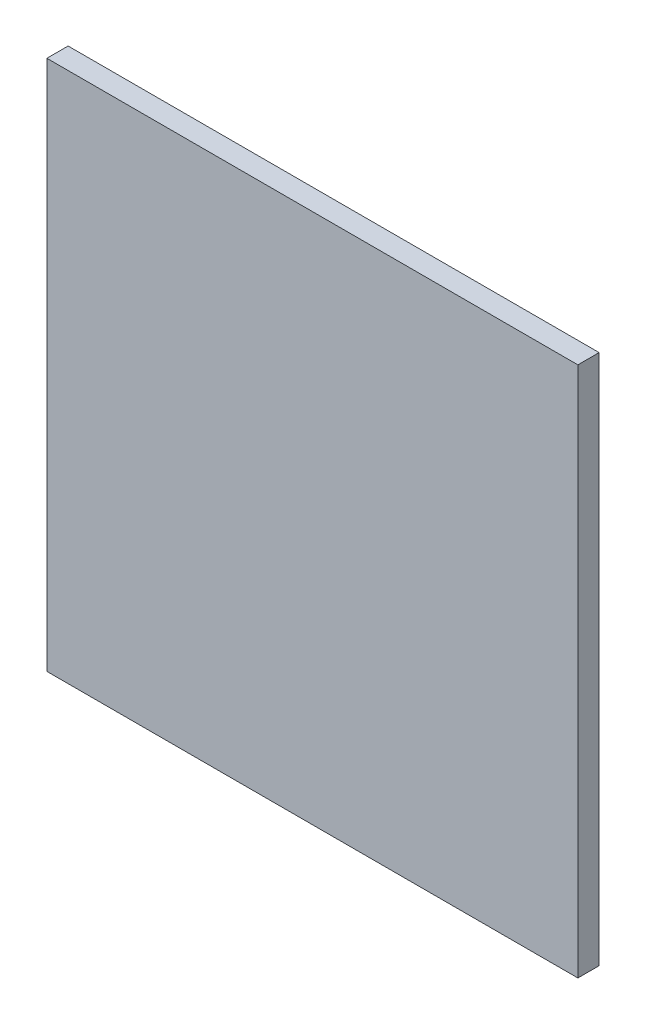
SolidWorks part; units mm, degrees
ref_plane "Ebene vorne" through (0, 0, 0) normal (0, 0, 1) x (1, 0, 0)
ref_plane "Ebene oben" through (0, 0, 0) normal (0, 1, 0) x (1, 0, 0)
ref_plane "Ebene rechts" through (0, 0, 0) normal (1, 0, 0) x (0, 0, -1)
sketch "Skizze2" plane through (0, 0, 0) normal (0, 0, 1) x (1, 0, 0)
  line L0 (-62.5, 62.5) -> (-62.5, -62.5) construction
  line L1 (-62.5, -62.5) -> (62.5, -62.5) construction
  line L2 (62.5, 62.5) -> (-62.5, 62.5) construction
  line L3 (62.5, -62.5) -> (62.5, 62.5) construction
  line L4 (-62.5, 62.5) -> (-62.5, -62.5)
  line L5 (-62.5, -62.5) -> (62.5, -62.5)
  line L6 (62.5, 62.5) -> (-62.5, 62.5)
  line L7 (62.5, -62.5) -> (62.5, 62.5)
extrude "Aufsatz-Linear austragen1" add sketch "Skizze2" along normal blind 5
